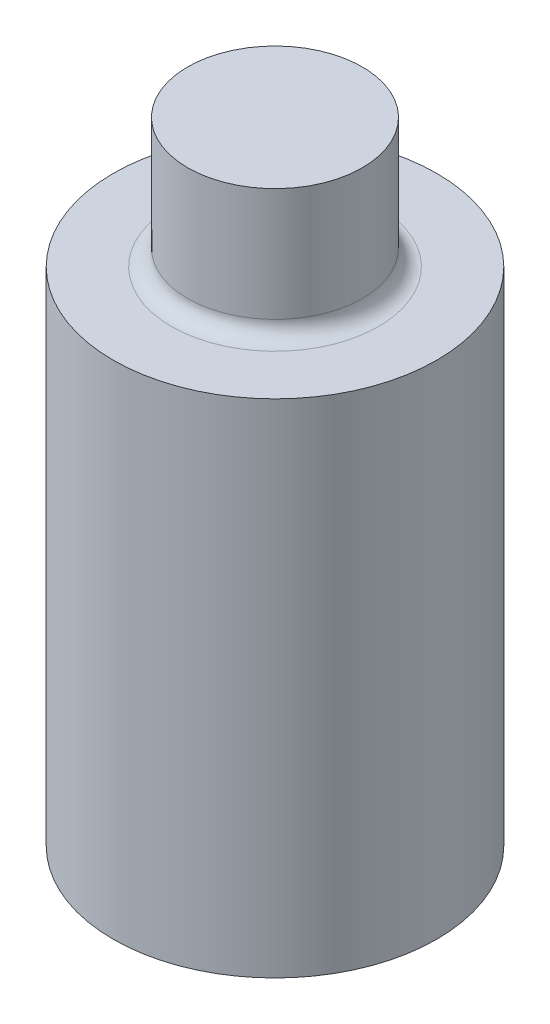
SolidWorks part; units mm, degrees
ref_plane "Front Plane" through (0, 0, 0) normal (0, 0, 1) x (1, 0, 0)
ref_plane "Top Plane" through (0, 0, 0) normal (0, 1, 0) x (1, 0, 0)
ref_plane "Right Plane" through (0, 0, 0) normal (1, 0, 0) x (0, 0, -1)
sketch "Sketch1" plane through (0, 0, 0) normal (0, 1, 0) x (1, 0, 0)
  circle A0 centre (0, 0) radius 5
  circle A1 centre (0, 0) radius 2.7
  dimension "D1" = 10
  dimension "D2" = 5.4
extrude "Boss-Extrude1" add sketch "Sketch1" along normal blind 15.5 contours A1 | A0 A1 region at (-4.8586, 0, 0) region at (0, 0, 0)
extrude "Boss-Extrude2" add sketch "Sketch1<4>" along normal blind 4 from surface contours A1 region at (0, 0, 0) starting at face at (0, 15.5, 5)
sketch "Sketch1<4>" plane through (0, 0, 0) normal (0, 1, 0) x (1, 0, 0) same geometry as "Sketch1"
fillet "Fillet1" radius 0.5 1 edges at (0, 15.5, 2.7)
